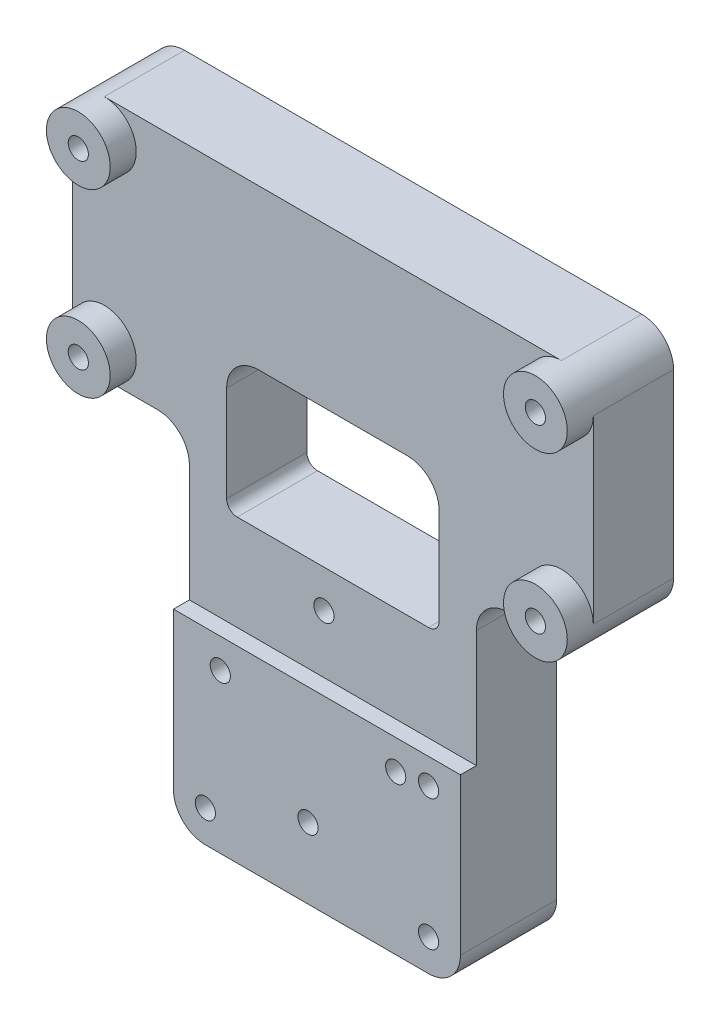
SolidWorks part; units mm, degrees
ref_plane "Front Plane" through (0, 0, 0) normal (0, 0, 1) x (1, 0, 0)
ref_plane "Top Plane" through (0, 0, 0) normal (0, 1, 0) x (1, 0, 0)
ref_plane "Right Plane" through (0, 0, 0) normal (1, 0, 0) x (0, 0, -1)
sketch "Sketch1" plane through (0, 0, 0) normal (0, 0, 1) x (1, 0, 0)
  line L1 (-23.657, 19.8) -> (-23.657, 36.8)
  line L2 (-20.657, 39.8) -> (22.343, 39.8)
  line L3 (25.343, 36.8) -> (25.343, 19.8)
  line L4 (11.343, -14.9) -> (-9.657, -14.9)
  line L5 (-12.657, -11.9) -> (-12.657, 13.8)
  line L6 (-15.657, 16.8) -> (-20.657, 16.8)
  line L7 (14.343, -11.9) -> (14.343, 13.8)
  line L8 (17.343, 16.8) -> (22.343, 16.8)
  arc A0 (-12.657, -11.9) -> (-9.657, -14.9) centre (-9.657, -11.9) ccw
  arc A1 (11.343, -14.9) -> (14.343, -11.9) centre (11.343, -11.9) ccw
  arc A2 (22.343, 16.8) -> (25.343, 19.8) centre (22.343, 19.8) ccw
  arc A3 (25.343, 36.8) -> (22.343, 39.8) centre (22.343, 36.8) ccw
  arc A4 (-20.657, 39.8) -> (-23.657, 36.8) centre (-20.657, 36.8) ccw
  arc A5 (-23.657, 19.8) -> (-20.657, 16.8) centre (-20.657, 19.8) ccw
  arc A6 (14.343, 13.8) -> (17.343, 16.8) centre (17.343, 13.8) cw
  arc A7 (-12.657, 13.8) -> (-15.657, 16.8) centre (-15.657, 13.8) ccw
  point P36 (11.343, -14.9)
  point P37 (-9.657, -14.9)
  dimension "D1" = 6
  dimension "D2" = 3
extrude "Boss-Extrude1" add sketch "Sketch1" along normal offset from surface (9.05 mm away) 0.15
sketch "Sketch2" plane through (0, 0, 9.05) normal (0, 0, 1) x (1, 0, 0)
  line L0 (-0.657, 19.8) -> (2.343, 19.8) construction
  line L3 (-9.157, 24.8) -> (10.843, 24.8)
  line L4 (-9.157, 24.8) -> (-9.157, 14.8)
  line L5 (-9.157, 14.8) -> (10.843, 14.8)
  line L6 (10.843, 24.8) -> (10.843, 14.8)
  line L7 (-9.157, 24.8) -> (10.843, 14.8) construction
  line L8 (-9.157, 14.8) -> (10.843, 24.8) construction
  line L9 (-9.157, 14.8) -> (-9.157, 12.8)
  line L12 (-8.157, 11.8) -> (9.843, 11.8)
  line L13 (10.843, 12.8) -> (10.843, 14.8)
  arc A4 (-9.157, 12.8) -> (-8.157, 11.8) centre (-8.157, 12.8) ccw
  arc A5 (9.843, 11.8) -> (10.843, 12.8) centre (9.843, 12.8) ccw
  point P0 (0.843, 19.8)
  dimension "D3" = 1
  dimension "D1" = 10
  dimension "D2" = 20
  dimension "D4" = 3
extrude "Cut-Extrude1" cut sketch "Sketch2" against normal through all contours L12 A5 L13 L5 L9 A4 | L6 L3 L4 L5 region at (0.843, 19.8, 9.05) region at (0.843, 13.3092, 9.05)
fillet "Fillet1" radius 3 2 edges at (10.843, 24.8, 4.525) (-9.157, 24.8, 4.525)
sketch "Sketch4" plane through (0, 0, 9.05) normal (0, 0, 1) x (1, 0, 0)
  circle A0 centre (22.343, 19.8) radius 3
  circle A1 centre (22.343, 36.8) radius 3
  circle A2 centre (-20.657, 36.8) radius 3
  circle A3 centre (-20.657, 19.8) radius 3
extrude "Boss-Extrude2" add sketch "Sketch4" along normal up to surface (0.95 mm away)
sketch "Sketch3" plane through (0, 0, 9.05) normal (0, 0, 1) x (1, 0, 0)
  line L7 (14.343, 2.8) -> (-12.657, 2.8)
  line L8 (-8.157, 11.8) -> (9.843, 11.8) construction
  line L15 (-20.657, 16.8) -> (-15.657, 16.8)
  line L16 (-12.657, 13.8) -> (-12.657, -11.9)
  line L17 (-9.657, -14.9) -> (11.343, -14.9)
  line L18 (14.343, -11.9) -> (14.343, 13.8)
  line L19 (17.343, 16.8) -> (22.343, 16.8)
  line L20 (25.343, 19.8) -> (25.343, 36.8)
  line L21 (22.343, 39.8) -> (-20.657, 39.8)
  line L22 (-23.657, 36.8) -> (-23.657, 19.8)
  line L23 (-20.657, 16.8) -> (-15.657, 16.8)
  line L24 (-12.657, 13.8) -> (-12.657, -11.9)
  line L25 (-9.657, -14.9) -> (11.343, -14.9)
  line L26 (14.343, -11.9) -> (14.343, 13.8)
  line L27 (17.343, 16.8) -> (22.343, 16.8)
  line L28 (25.343, 19.8) -> (25.343, 36.8)
  line L29 (22.343, 39.8) -> (-20.657, 39.8)
  line L30 (-23.657, 36.8) -> (-23.657, 19.8)
  arc A8 (-12.657, 13.8) -> (-15.657, 16.8) centre (-15.657, 13.8) ccw
  arc A9 (-12.657, -11.9) -> (-9.657, -14.9) centre (-9.657, -11.9) ccw
  arc A10 (11.343, -14.9) -> (14.343, -11.9) centre (11.343, -11.9) ccw
  arc A11 (17.343, 16.8) -> (14.343, 13.8) centre (17.343, 13.8) ccw
  arc A12 (25.343, 19.8) -> (22.343, 16.8) centre (22.343, 19.8) ccw
  arc A13 (22.343, 39.8) -> (25.343, 36.8) centre (22.343, 36.8) ccw
  arc A14 (-23.657, 36.8) -> (-20.657, 39.8) centre (-20.657, 36.8) ccw
  arc A15 (-20.657, 16.8) -> (-23.657, 19.8) centre (-20.657, 19.8) ccw
  arc A16 (-12.657, 13.8) -> (-15.657, 16.8) centre (-15.657, 13.8) ccw
  arc A17 (-12.657, -11.9) -> (-9.657, -14.9) centre (-9.657, -11.9) ccw
  arc A18 (11.343, -14.9) -> (14.343, -11.9) centre (11.343, -11.9) ccw
  arc A19 (17.343, 16.8) -> (14.343, 13.8) centre (17.343, 13.8) ccw
  arc A20 (25.343, 19.8) -> (22.343, 16.8) centre (22.343, 19.8) ccw
  arc A21 (22.343, 39.8) -> (25.343, 36.8) centre (22.343, 36.8) ccw
  arc A22 (-23.657, 36.8) -> (-20.657, 39.8) centre (-20.657, 36.8) ccw
  arc A23 (-20.657, 16.8) -> (-23.657, 19.8) centre (-20.657, 19.8) ccw
  arc M5 (10.843, 12.8) -> (9.843, 11.8) centre (9.843, 12.8) cw
  line M6 (9.843, 11.8) -> (-8.157, 11.8)
  arc M7 (-8.157, 11.8) -> (-9.157, 12.8) centre (-8.157, 12.8) cw
  line M8 (-9.157, 12.8) -> (-9.157, 21.8)
  arc M9 (-9.157, 21.8) -> (-6.157, 24.8) centre (-6.157, 21.8) cw
  line M10 (-6.157, 24.8) -> (7.843, 24.8)
  arc M11 (7.843, 24.8) -> (10.843, 21.8) centre (7.843, 21.8) cw
  line M12 (10.843, 21.8) -> (10.843, 12.8)
  line M13 (-20.657, 16.8) -> (-15.657, 16.8)
  arc M14 (-15.657, 16.8) -> (-12.657, 13.8) centre (-15.657, 13.8) cw
  line M15 (-12.657, 13.8) -> (-12.657, -11.9)
  line M19 (14.343, -11.9) -> (14.343, 13.8)
  arc M20 (14.343, 13.8) -> (17.343, 16.8) centre (17.343, 13.8) cw
  line M21 (17.343, 16.8) -> (22.343, 16.8)
  arc M22 (22.343, 16.8) -> (25.343, 19.8) centre (22.343, 19.8) cw
  line M23 (25.343, 19.8) -> (25.343, 36.8)
  arc M24 (25.343, 36.8) -> (22.343, 39.8) centre (22.343, 36.8) cw
  line M25 (22.343, 39.8) -> (-20.657, 39.8)
  arc M26 (-20.657, 39.8) -> (-23.657, 36.8) centre (-20.657, 36.8) cw
  line M27 (-23.657, 36.8) -> (-23.657, 19.8)
  arc M28 (-23.657, 19.8) -> (-20.657, 16.8) centre (-20.657, 19.8) cw
  dimension "D1" = 0
  dimension "D2" = 9
extrude "Cut-Extrude2" cut sketch "Sketch3" against normal blind 1.5 contours L7 M19 M20 M21 M22 M23 M24 M25 M26 M27 M28 M13 M14 M15 M12 M5 M6 M7 M8 M9 M10 M11 region at (0.843, 3.414, 9.05)
sketch "Sketch5" plane through (0, 0, 10) normal (0, 0, 1) x (1, 0, 0)
  circle A0 centre (22.343, 36.8) radius 0.95
  circle A1 centre (22.343, 19.8) radius 0.95
  circle A2 centre (-20.657, 36.8) radius 0.95
  circle A3 centre (-20.657, 19.8) radius 0.95
  circle A4 centre (-9.657, -11.9) radius 0.95
  circle A5 centre (11.343, -11.9) radius 0.95
  circle A6 centre (11.343, 0.4) radius 0.95
  circle A7 centre (0, 8.25) radius 0.95
  circle A8 centre (-8.25, 0) radius 0.95
  circle A9 centre (8.25, 0) radius 0.95
  circle A10 centre (0, -8.25) radius 0.95
  point P31 (11.343, 0.4)
  point P33 (0, -8.25)
  point P35 (-8.0437, -0.4063)
  point P36 (-8.25, -0.3358)
  point P37 (0, 0)
  point P38 (-8.25, 0)
  dimension "D1" = 1.9
extrude "Cut-Extrude3" cut sketch "Sketch5" against normal through all
